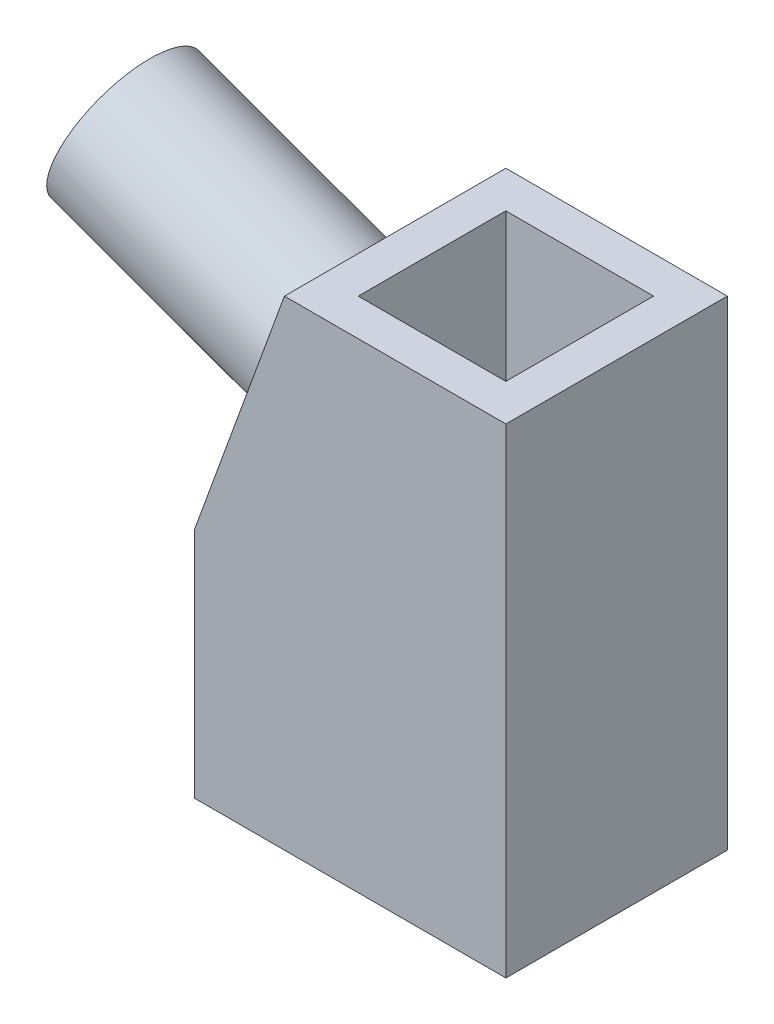
SolidWorks part; units mm, degrees
ref_plane "Front Plane" through (0, 0, 0) normal (0, 0, 1) x (1, 0, 0)
ref_plane "Top Plane" through (0, 0, 0) normal (0, 1, 0) x (1, 0, 0)
ref_plane "Right Plane" through (0, 0, 0) normal (1, 0, 0) x (0, 0, -1)
sketch "Sketch1" plane through (0, 0, 0) normal (0, 1, 0) x (1, 0, 0)
  line L1 (0, 0) -> (53.594, 0)
  line L2 (0, 0) -> (0, 38.1)
  line L3 (0, 38.1) -> (53.594, 38.1)
  line L4 (53.594, 0) -> (53.594, 38.1)
  dimension "D1" = 53.594
  dimension "D2" = 38.1
extrude "Boss-Extrude1" add sketch "Sketch1" along normal blind 82.55
sketch "Sketch4" plane through (0, 0, 0) normal (0, 0, 1) x (1, 0, 0)
  line L0 (53.594, 82.55) -> (15.494, 82.55)
  line L1 (0, 82.55) -> (53.594, 82.55) construction
  line L2 (15.494, 82.55) -> (-13.2573, 3.5565)
  line L3 (0, 82.55) -> (0, 39.9806)
  line L4 (0, 82.55) -> (0, 0) construction
  line L5 (15.494, 82.55) -> (0, 82.55)
  line M5 (53.594, 82.55) -> (0, 82.55)
  line M6 (0, 82.55) -> (0, 0)
  dimension "D1" = 38.1
  dimension "D2" = 110
extrude "Cut-Extrude1" cut sketch "Sketch4" against normal through all contours L2 M5 M6 region at (5.1647, 68.3602, 0)
sketch "Sketch5" plane through (0, 82.55, 0) normal (0, 1, 0) x (1, 0, 0)
  line L0 (53.594, 0) -> (53.594, 38.1) construction
  line L1 (21.844, 31.75) -> (47.244, 31.75)
  line L2 (21.844, 31.75) -> (21.844, 6.35)
  line L3 (21.844, 6.35) -> (47.244, 6.35)
  line L4 (47.244, 31.75) -> (47.244, 6.35)
  line L5 (53.594, 38.1) -> (15.494, 38.1) construction
  dimension "D1" = 25.4
  dimension "D2" = 25.4
  dimension "D3" = 6.35
  dimension "D4" = 6.35
extrude "Cut-Extrude2" cut sketch "Sketch5" against normal through all
sketch "Sketch6" plane through (-12.8495, 4.6768, 0) normal (-0.9397, 0.342, 0) x (0, 0, 1)
  line L3 (-38.1, 82.8709) -> (-38.1, 37.5695)
  line L4 (-38.1, 37.5695) -> (0, 37.5695)
  circle A0 centre (-19.05, 60.2202) radius 12.7
  point P2 (-38.1, 60.2202)
  point P3 (-19.05, 37.5695)
  dimension "D2" = 25.4
extrude "Boss-Extrude2" add sketch "Sketch6" along normal blind 41.275 contours A0 region at (7.747, 61.2653, -19.05)
ref_axis "Axis1" through (-26.5017, 73.7308, -19.05) along (0.9397, -0.342, 0)
